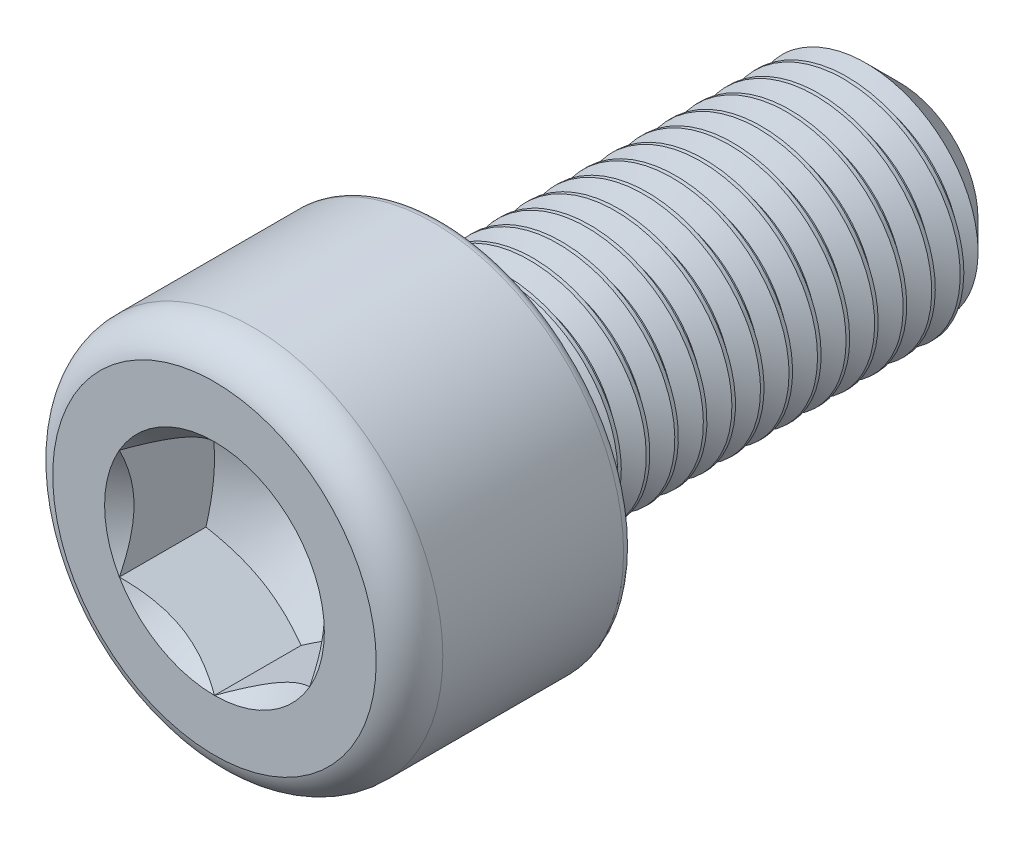
SolidWorks part; units mm, degrees
ref_plane "Front Plane" through (0, 0, 0) normal (0, 0, 1) x (1, 0, 0)
ref_plane "Top Plane" through (0, 0, 0) normal (0, 1, 0) x (1, 0, 0)
ref_plane "Right Plane" through (0, 0, 0) normal (1, 0, 0) x (0, 0, -1)
sketch "Sketch1" plane through (0, 0, 0) normal (1, 0, 0) x (0, 0, -1)
  line L0 (-6, 0) -> (0, 0) construction
  line L1 (0, 0) -> (12, 0) construction
  line L2 (-6, 2.5) -> (-6, -2.5) construction
  line L3 (0, 5) -> (0, -5) construction
  line L4 (0, 5) -> (-6, 5) construction
  line L5 (12, 3) -> (12, -3) construction
  line L6 (12, 3) -> (12.75, 3) construction
  line L7 (12, 3) -> (10.125, 3) construction
  line L8 (-6, -2.5) -> (-3.5, -2.5) construction
  line L9 (10.125, 3) -> (10.125, -3) construction
  dimension "Length" = 12
  dimension "Thread Pitch" = 0.75
  dimension "D3" = 1.875
  dimension "Head Height" = 6
  dimension "Drive Size" = 5
  dimension "Head Diameter" = 10
  dimension "Thread Size" = 6
  dimension "D1" = 2.5
sketch "Sketch2" plane through (0, 0, 0) normal (1, 0, 0) x (0, 0, -1)
  line L2 (-6, 4.25) -> (-6, 2.5)
  line L3 (-6, 2.5) -> (-3.5, 2.5)
  line L4 (-3.5, 2.5) -> (-2.0566, 0)
  line L5 (-6, 0) -> (0, 0) construction
  line L6 (-2.0566, 0) -> (12, 0)
  line L7 (12, 0) -> (12, 2.0625)
  line L8 (12, 3) -> (12, -3) construction
  line L9 (12, 2.0625) -> (11.0625, 3)
  line L10 (12, 3) -> (10.125, 3) construction
  line L11 (11.0625, 3) -> (0, 3)
  line L12 (0, 5) -> (0, -5) construction
  line L13 (0, 3) -> (0, 5)
  line L14 (0, 5) -> (-5, 5)
  arc A0 (-5, 5) -> (-6, 4.25) centre (-5, 3.9583) ccw
  dimension "D1" = 45
  dimension "D2" = 0.9375
  dimension "D3" = 30
  dimension "D5" = 0.75
revolve "Revolve1" add sketch "Sketch2" angle 360 about L6
fillet "Fillet2" radius 0.25 1 edges at (5, 0, 0)
sketch "Sketch3" plane through (0, 0, 6) normal (0, 0, 1) x (1, 0, 0)
  line L1 (0, 2.8868) -> (-2.5, 1.4434)
  line L2 (-2.5, 1.4434) -> (-2.5, -1.4434)
  line L3 (-2.5, -1.4434) -> (0, -2.8868)
  line L4 (0, -2.8868) -> (2.5, -1.4434)
  line L5 (2.5, -1.4434) -> (2.5, 1.4434)
  line L6 (2.5, 1.4434) -> (0, 2.8868)
  circle A0 centre (0, 0) radius 2.5 construction
  circle A1 centre (0, 0) radius 2.5 construction
extrude "Cut-Extrude1" cut sketch "Sketch3" against normal up to surface (2.2767 mm away)
sketch "Sketch4" plane through (0, 0, 6) normal (0, 0, 1) x (1, 0, 0)
  circle A0 centre (0, 0) radius 2.8868
extrude "Cut-Extrude2" cut sketch "Sketch4" against normal through all draft 45
split "Split1" bodies to split 106 resulting bodies 107 108 split by face at (4.75, 0, 0)
sketch "Sketch5" plane through (0, 0, -12) normal (0, 0, -1) x (-1, 0, 0)
  circle A0 centre (0, 0) radius 3 construction
  circle A1 centre (0, 0) radius 3
curve "Helix/Spiral1" pitch 0.75 height 12.75 radius 3 centre (0, 0, -12) axis (0, 0, 1) start towards (0, 1, 0)
sketch "Sketch6" plane through (0, 0, 0) normal (1, 0, 0) x (0, 0, -1)
  line L0 (11.9531, 3.0812) -> (12.3281, 2.4317) construction
  line L1 (12.3281, 2.4317) -> (12.7031, 3.0812) construction
  line L2 (12.7031, 3.0812) -> (11.9531, 3.0812) construction
  line L3 (12, 3) -> (12.6562, 3) construction
  line L4 (12.3281, 3.0812) -> (12.3281, 3) construction
  line L5 (12.3281, 3) -> (12.3281, 2.5129) construction
  line L6 (12.3281, 2.5129) -> (12.3281, 2.4317) construction
  line L7 (12.2812, 2.5129) -> (12.375, 2.5129)
  line L8 (11.9766, 3.0406) -> (12.6797, 3.0406)
  line L9 (12.375, 2.5129) -> (12.6797, 3.0406)
  line L10 (12.2812, 2.5129) -> (11.9766, 3.0406)
  point P12 (12.3281, 3.0406)
  dimension "D1" = 0.75
sweep "Cut-Sweep1" cut profiles "Sketch6" path "Helix/Spiral1" align with end faces yes
sketch "Sketch7" plane through (0, 0, 0) normal (0, 0, -1) x (-1, 0, 0)
  circle A1 centre (0, 0) radius 3
  circle A2 centre (0, 0) radius 3
  dimension "D1" = 0
extrude "Boss-Extrude1" add sketch "Sketch7" along normal through all draft 45
equation "\"D3@Sketch1\" = \"Thread Pitch@Sketch1\" * 2.5"
equation "\"D1@Sketch1\"=\"Drive Size@Sketch1\"*.5"
equation "\"D2@Sketch2\"=\"Thread Pitch@Sketch1\"*1.25"
equation "\"D3@Helix/Spiral1\"=\"Length@Sketch1\"+\"Thread Pitch@Sketch1\""
equation "\"D4@Helix/Spiral1\"=\"Thread Pitch@Sketch1\""
equation "\"D2@Sketch6\"=\"D1@Sketch6\"/8"
equation "\"D1@Sketch6\"=\"Thread Pitch@Sketch1\""
equation "\"D4@Sketch2\"=\"Head Height@Sketch1\"/6"
equation "\"D5@Sketch2\"=\"D4@Sketch2\"*.75"
equation "\"D1@Fillet2\"=\"D4@Sketch2\"/4"
